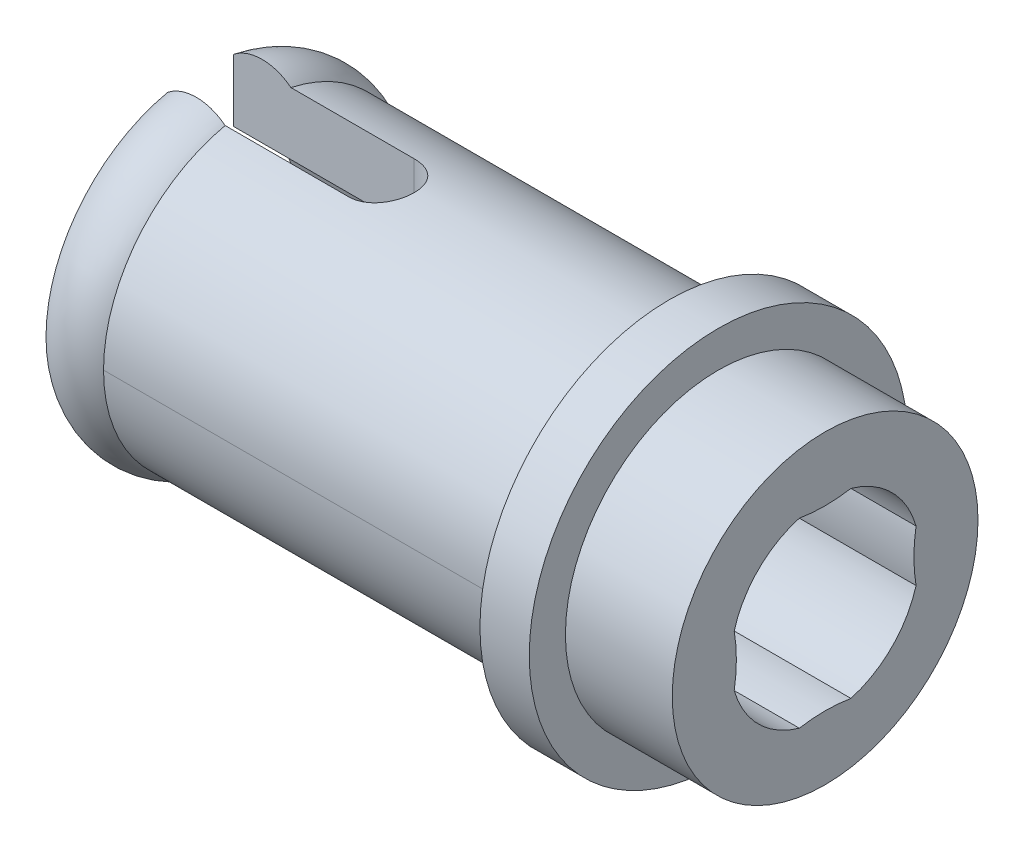
SolidWorks part; units mm, degrees
ref_plane "Front" through (0, 0, 0) normal (0, 0, 1) x (1, 0, 0)
ref_plane "Top" through (0, 0, 0) normal (0, 1, 0) x (1, 0, 0)
ref_plane "Right" through (0, 0, 0) normal (1, 0, 0) x (0, 0, -1)
sketch "Sketch1" plane through (0, 0, 0) normal (1, 0, 0) x (0, 0, -1)
  circle A0 centre (0, 0) radius 2.3622
  dimension "D1" = 4.7244
extrude "Base-Extrude" add sketch "Sketch1" along normal blind 1.651
sketch "Sketch3" plane through (0, 0, 0) normal (-1, 0, 0) x (0, 0, 1)
  circle A0 centre (0, 0) radius 2.921
  dimension "D1" = 5.842
extrude "Boss-Extrude1" add sketch "Sketch3" along normal blind 0.762
sketch "Sketch4" plane through (-0.762, 0, 0) normal (-1, 0, 0) x (0, 0, 1)
  circle A0 centre (0, 0) radius 2.3876
  dimension "D1" = 4.7752
extrude "Boss-Extrude2" add sketch "Sketch4" along normal blind 7.239
split line "Split Line1"
ref_plane "Plane1" through (-0.508, 0, 0) normal (1, 0, 0) x (0, 0, -1)
sketch "Sketch6" plane through (0, 0, 0) normal (0, 1, 0) x (1, 0, 0)
  line L0 (-0.762, 2.3876) -> (-8.001, 2.3876) construction
  line L1 (0, 0) -> (-8.8014, 0) construction
  line L2 (-8.001, 2.3876) -> (-7.112, 2.3876)
  arc A0 (-8.001, 2.3876) -> (-7.112, 2.3876) centre (-7.5565, 1.8156) cw
  dimension "D1" = 0.889
  dimension "D2" = 5.08
revolve "Boss-Revolve2" add sketch "Sketch6" angle 360 about L1
sketch "Sketch7" plane through (-8.001, 0, 0) normal (-1, 0, 0) x (0, 0, 1)
  circle A0 centre (0, 0) radius 1.4605
  dimension "D1" = 2.921
extrude "Cut-Extrude2" cut sketch "Sketch7" against normal through all
sketch "Sketch8" plane through (0, 0, 0) normal (0, 1, 0) x (1, 0, 0)
  line L0 (0, 0) -> (-8.8999, 0) construction
  line L1 (-8.001, 0.508) -> (-5.207, 0.508)
  line L3 (-5.207, -0.508) -> (-8.001, -0.508)
  line L4 (-8.001, -0.508) -> (-8.001, 0.508)
  line L5 (-8.001, -2.3876) -> (-8.001, 2.3876) construction
  arc A0 (-5.207, 0.508) -> (-5.207, -0.508) centre (-5.207, 0) cw
  dimension "D1" = 1.016
  dimension "D2" = 2.794
extrude "Cut-Extrude4" cut sketch "Sketch8" against normal through all and the other way through all
sketch "Sketch11" plane through (1.651, 0, 0) normal (1, 0, 0) x (0, 0, -1)
  line L0 (0, 0) -> (3.0369, 0) construction
  line L1 (0, 0) -> (0, 3.3772) construction
  circle A0 centre (0, 0) radius 1.4605 construction
  arc A1 (0.3985, 1.4051) -> (-0.3985, 1.4051) centre (0, 0) ccw
  arc A2 (0.3985, 1.4051) -> (-0.3985, 1.4051) centre (0, 3.7592) cw
  dimension "D1" = 4.7752
  dimension "D2" = 3.7592
extrude "Boss-Extrude11" add sketch "Sketch11" against normal blind 3.937
pattern_circular "CirPattern1" count 4 every 90 about axis through (1.651, 0, 0) along (-1, 0, 0) of "Boss-Extrude11"
